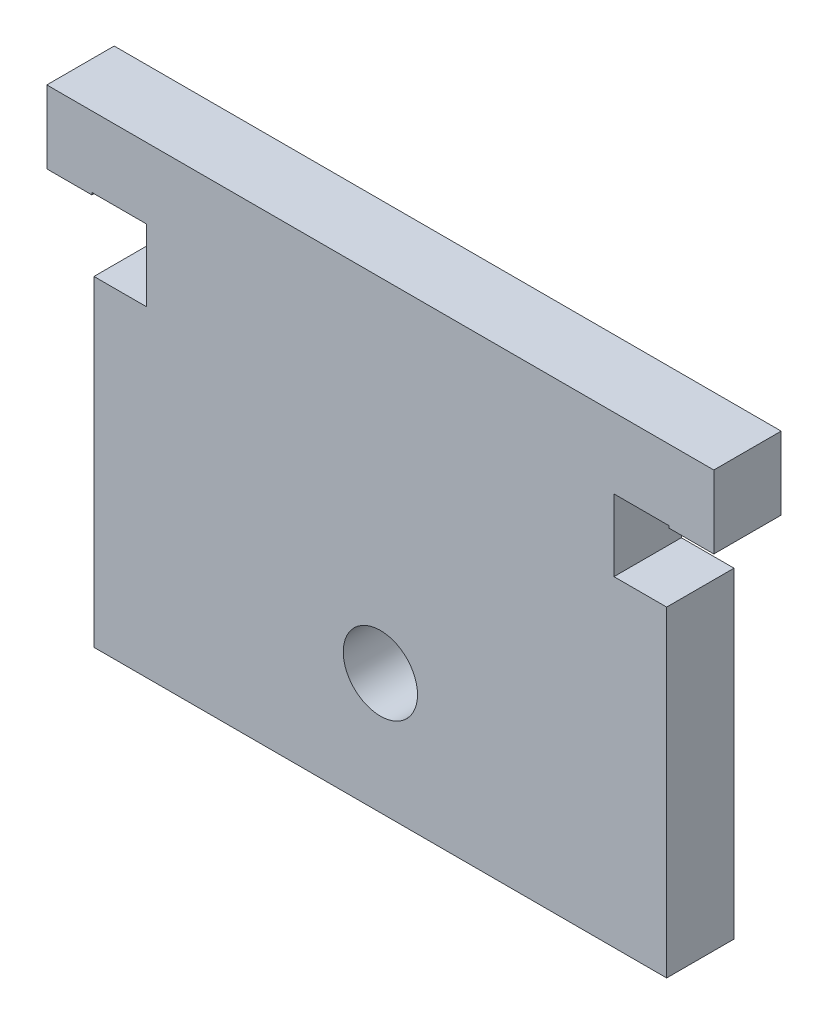
SolidWorks part; units mm, degrees
material "AISI 4130 Steel, annealed at 865C"
ref_plane "X-Y Datum" through (0, 0, 0) normal (0, 0, 1) x (1, 0, 0)
ref_plane "X-Z Datum" through (0, 0, 0) normal (0, 1, 0) x (1, 0, 0)
ref_plane "Y-Z Datum" through (0, 0, 0) normal (1, 0, 0) x (0, 0, -1)
sketch "Sketch1" plane through (0, 0, 0) normal (0, 0, 1) x (1, 0, 0)
  line L1 (-42.8625, -25.4) -> (42.8625, -25.4)
  line L2 (-42.8625, -25.4) -> (-42.8625, 25.4)
  line L3 (-42.8625, 25.4) -> (42.8625, 25.4)
  line L4 (42.8625, -25.4) -> (42.8625, 25.4)
  line L5 (-42.8625, -25.4) -> (42.8625, 25.4) construction
  line L6 (-42.8625, 25.4) -> (42.8625, -25.4) construction
  point P0 (0, 0)
  dimension "D1" = 85.725
  dimension "D2" = 50.8
extrude "Boss-Extrude1" add sketch "Sketch1" along normal blind 6.35
sketch "Sketch2" plane through (0, 0, 6.35) normal (0, 0, 1) x (1, 0, 0)
  line L1 (-42.8625, -25.4) -> (-26.9875, -25.4)
  line L2 (-42.8625, -25.4) -> (-42.8625, 17.78)
  line L3 (-42.8625, 17.78) -> (-26.9875, 17.78)
  line L4 (-26.9875, -25.4) -> (-26.9875, 17.78)
  line L5 (42.8625, -25.4) -> (26.9875, -25.4)
  line L6 (42.8625, -25.4) -> (42.8625, 17.78)
  line L7 (42.8625, 17.78) -> (26.9875, 17.78)
  line L8 (26.9875, -25.4) -> (26.9875, 17.78)
  dimension "D1" = 15.875
  dimension "D2" = 43.18
extrude "Cut-Extrude1" cut sketch "Sketch2" against normal blind 6.35
sketch "Sketch3" plane through (0, 25.4, 0) normal (0, 1, 0) x (1, 0, 0)
  line L1 (-42.8625, 0) -> (42.8625, 0)
  line L2 (-42.8625, 0) -> (-42.8625, -6.35)
  line L3 (-42.8625, -6.35) -> (42.8625, -6.35)
  line L4 (42.8625, 0) -> (42.8625, -6.35)
extrude "Cut-Extrude2" cut sketch "Sketch3" against normal blind 0.762
sketch "Sketch5" plane through (-26.9875, 0, 0) normal (-1, 0, 0) x (0, 0, 1)
  line L0 (6.35, -25.4) -> (6.35, 17.78) construction
  line L1 (0, 17.78) -> (6.35, 17.78)
  line L2 (0, 17.78) -> (0, 11.43)
  line L3 (0, 11.43) -> (6.35, 11.43)
  line L4 (6.35, 17.78) -> (6.35, 11.43)
  dimension "D1" = 6.35
extrude "Cut-Extrude3" cut sketch "Sketch5" against normal blind 4.7625
mirror "Mirror1" about plane through (0, 0, 0) normal (1, 0, 0) of "Cut-Extrude3"
sketch "Sketch6" plane through (0, 0, 6.35) normal (0, 0, 1) x (1, 0, 0)
  line L12 (26.9875, 11.43) -> (22.225, 11.43)
  line L13 (22.225, 11.43) -> (22.225, 17.78)
  line L14 (22.225, 17.78) -> (42.8625, 17.78)
  line L15 (42.8625, 17.78) -> (42.8625, 24.638)
  line L16 (42.8625, 24.638) -> (-42.8625, 24.638)
  line L17 (-42.8625, 24.638) -> (-42.8625, 17.78)
  line L18 (-42.8625, 17.78) -> (-22.225, 17.78)
  line L19 (-22.225, 17.78) -> (-22.225, 11.43)
  line L20 (-22.225, 11.43) -> (-26.9875, 11.43)
  line L21 (-26.9875, 11.43) -> (-26.9875, -25.4)
  line L22 (-26.9875, -25.4) -> (26.9875, -25.4)
  line L23 (26.9875, -25.4) -> (26.9875, 11.43)
  line L24 (26.9875, 11.43) -> (22.225, 11.43)
  line L25 (22.225, 11.43) -> (22.225, 17.78)
  line L26 (22.225, 17.78) -> (42.8625, 17.78)
  line L27 (42.8625, 17.78) -> (42.8625, 24.638)
  line L28 (42.8625, 24.638) -> (-42.8625, 24.638)
  line L29 (-42.8625, 24.638) -> (-42.8625, 17.78)
  line L30 (-42.8625, 17.78) -> (-22.225, 17.78)
  line L31 (-22.225, 17.78) -> (-22.225, 11.43)
  line L32 (-22.225, 11.43) -> (-26.9875, 11.43)
  line L33 (-26.9875, 11.43) -> (-26.9875, -25.4)
  line L34 (-26.9875, -25.4) -> (26.9875, -25.4)
  line L35 (26.9875, -25.4) -> (26.9875, 11.43)
  circle A1 centre (0.0059, -7.6663) radius 3.5
  dimension "D2" = 17.7337
  dimension "D1" = 0
sketch "Sketch7" plane through (-42.8625, 0, 0) normal (-1, 0, 0) x (0, 0, 1)
  line L1 (0, 24.638) -> (6.35, 24.638)
  line L2 (0, 24.638) -> (0, 17.78)
  line L3 (0, 17.78) -> (6.35, 17.78)
  line L4 (6.35, 24.638) -> (6.35, 17.78)
extrude "Cut-Extrude5" cut sketch "Sketch7" against normal blind 11.43
mirror "Mirror2" about plane through (0, 0, 0) normal (1, 0, 0) of "Cut-Extrude5"
sketch "Sketch8" plane through (0, -25.4, 0) normal (0, -1, 0) x (1, 0, 0)
  line L7 (-26.9875, 6.35) -> (26.9875, 6.35)
  line L8 (-26.9875, 6.35) -> (-26.9875, 0)
  line L9 (-26.9875, 0) -> (26.9875, 0)
  line L10 (26.9875, 6.35) -> (26.9875, 0)
extrude "Cut-Extrude6" cut sketch "Sketch8" against normal blind 6.35
hole_wizard "M6 Clearance Hole1" positions "Sketch13" profile "Sketch10" hole size "M6" standard "ANSI Metric" end condition through all
sketch "Sketch13" plane through (0, 0, 6.35) normal (0, 0, 1) x (1, 0, 0)
  point P0 (0.0059, -7.6663)
sketch "Sketch10" plane through (0.0059, -7.6663, 6.35) normal (1, 0, 0) x (0, -1, 0)
  line L0 (0, 0) -> (0, 6.35)
  line L1 (0, 6.35) -> (3.5, 6.35)
  line L2 (3.5, 6.35) -> (3.5, 0)
  line L5 (3.5, 0) -> (0, 0)
  line L11 (0, -6.35) -> (0, 107.95) construction
  dimension "Thru Hole Dia." = 7
  dimension "Thru Hole Depth" = 6.35
sketch "Sketch12" plane through (0, 0, 6.35) normal (0, 0, 1) x (1, 0, 0)
  line L0 (-22.0218, 17.9832) -> (-27.1907, 17.9832)
  line L1 (-22.225, 17.78) -> (-26.9875, 17.78) construction
  line L2 (-22.225, 17.78) -> (-22.225, 11.43) construction
  line L3 (-22.225, 11.43) -> (-26.9875, 11.43) construction
  line L4 (-26.9875, 17.78) -> (-26.9875, 11.43) construction
  line L5 (22.225, 17.78) -> (26.9875, 17.78) construction
  line L6 (22.225, 17.78) -> (22.225, 11.43) construction
  line L7 (22.225, 11.43) -> (26.9875, 11.43) construction
  line L8 (26.9875, 17.78) -> (26.9875, 11.43) construction
  line L9 (-27.1907, 17.9832) -> (-27.1907, 11.2268)
  line L10 (-22.0218, 11.2268) -> (-27.1907, 11.2268)
  line L11 (-22.0218, 17.9832) -> (-22.0218, 11.2268)
  line L12 (-26.9875, -19.05) -> (26.9875, -19.05)
  line L13 (26.9875, -19.05) -> (26.9875, 11.43)
  line L14 (26.9875, 11.43) -> (22.225, 11.43)
  line L15 (22.225, 11.43) -> (22.225, 17.78)
  line L16 (22.225, 17.78) -> (31.4325, 17.78)
  line L17 (31.4325, 17.78) -> (31.4325, 24.638)
  line L18 (31.4325, 24.638) -> (-31.4325, 24.638)
  line L19 (-31.4325, 24.638) -> (-31.4325, 17.78)
  line L20 (-31.4325, 17.78) -> (-22.225, 17.78)
  line L21 (-22.225, 17.78) -> (-22.225, 11.43)
  line L22 (-22.225, 11.43) -> (-26.9875, 11.43)
  line L23 (-26.9875, 11.43) -> (-26.9875, -19.05)
  line L24 (-26.9875, -19.05) -> (26.9875, -19.05) construction
  line L25 (26.9875, -19.05) -> (26.9875, 11.43) construction
  line L26 (26.9875, 11.43) -> (22.225, 11.43) construction
  line L27 (22.225, 11.43) -> (22.225, 17.78) construction
  line L28 (22.225, 17.78) -> (31.4325, 17.78) construction
  line L29 (31.4325, 17.78) -> (31.4325, 24.638) construction
  line L30 (31.4325, 24.638) -> (-31.4325, 24.638) construction
  line L31 (-31.4325, 24.638) -> (-31.4325, 17.78) construction
  line L32 (-31.4325, 17.78) -> (-22.225, 17.78) construction
  line L33 (-22.225, 17.78) -> (-22.225, 11.43) construction
  line L34 (-22.225, 11.43) -> (-26.9875, 11.43) construction
  line L35 (-26.9875, 11.43) -> (-26.9875, -19.05) construction
  line L36 (22.0218, 17.9832) -> (22.0218, 11.2268)
  line L37 (22.0218, 11.2268) -> (27.1907, 11.2268)
  line L38 (27.1907, 17.9832) -> (27.1907, 11.2268)
  line L39 (22.0218, 17.9832) -> (27.1907, 17.9832)
  dimension "D1" = 0
  dimension "D2" = 0.2032
extrude "Cut-Extrude7" cut sketch "Sketch12" against normal through all
